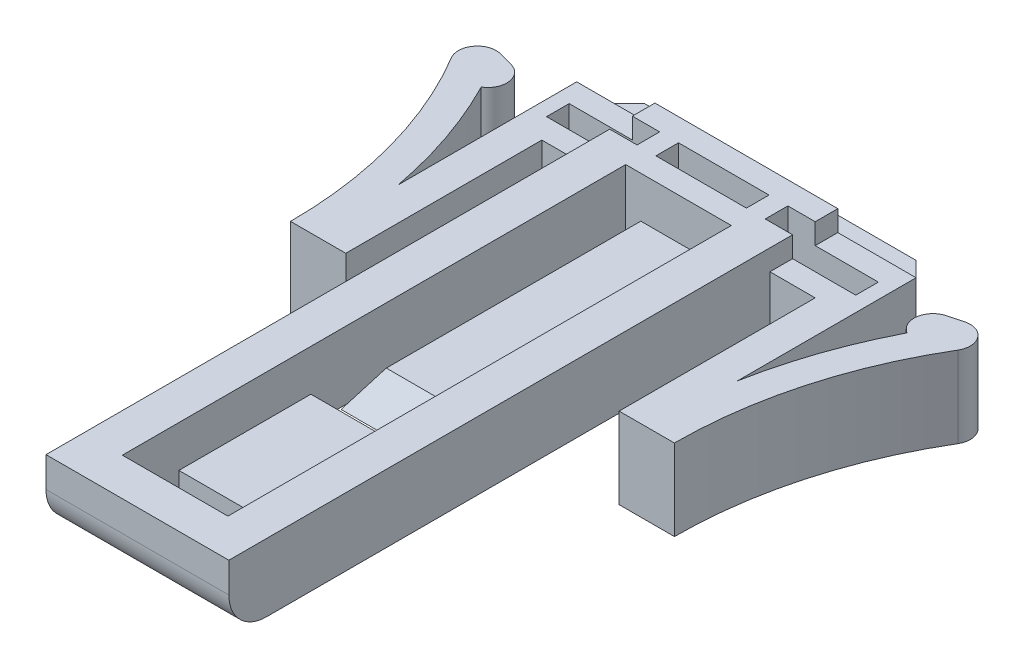
SolidWorks part; units mm, degrees
ref_plane "Спереди" through (0, 0, 0) normal (0, 0, 1) x (1, 0, 0)
ref_plane "Сверху" through (0, 0, 0) normal (0, 1, 0) x (1, 0, 0)
ref_plane "Справа" through (0, 0, 0) normal (1, 0, 0) x (0, 0, -1)
sketch "Эскиз1" plane through (0, 0, 0) normal (0, 1, 0) x (1, 0, 0)
  line L0 (0, 0) -> (0, 16.15) construction
  line L1 (4.85, 16.15) -> (-4.85, 16.15)
  line L2 (4.85, 16.15) -> (4.85, -16.15)
  line L3 (4.85, -16.15) -> (-4.85, -16.15)
  line L4 (-4.85, 16.15) -> (-4.85, -16.15)
  line L5 (4.85, 16.15) -> (-4.85, -16.15) construction
  line L6 (4.85, -16.15) -> (-4.85, 16.15) construction
  line L7 (-2.4, 14.95) -> (2.4, 14.95)
  line L8 (-2.4, 14.95) -> (-2.4, 13.75)
  line L9 (-2.4, 13.75) -> (2.4, 13.75)
  line L10 (2.4, 14.95) -> (2.4, 13.75)
  line L11 (4.85, 13.75) -> (3.4, 13.75)
  line L12 (4.85, 13.75) -> (4.85, 14.95)
  line L13 (4.85, 14.95) -> (3.4, 14.95)
  line L14 (3.4, 13.75) -> (3.4, 14.95)
  line L15 (-4.85, 13.75) -> (-3.4, 13.75)
  line L16 (-4.85, 13.75) -> (-4.85, 14.95)
  line L17 (-4.85, 14.95) -> (-3.4, 14.95)
  line L18 (-3.4, 13.75) -> (-3.4, 14.95)
  line L19 (-2, 12.55) -> (-2, -3.35)
  line L20 (-2.8, -14.15) -> (2.8, -14.15)
  line L21 (-2.8, -14.15) -> (-2.8, -11.15)
  line L22 (-2.8, -11.15) -> (2.8, -11.15)
  line L23 (2.8, -14.15) -> (2.8, -11.15)
  line L24 (2.8, -4.15) -> (-2.8, -4.15)
  line L25 (2.8, -4.15) -> (2.8, 12.55)
  line L26 (2.8, 12.55) -> (-2.8, 12.55)
  line L27 (-2.8, -4.15) -> (-2.8, 12.55)
  line L28 (-2, -3.35) -> (2, -3.35)
  line L29 (2, -3.35) -> (2, 12.55)
  point P0 (0, 0)
  dimension "D1" = 9.7
  dimension "D2" = 32.3
  dimension "D3" = 1.2
  dimension "D4" = 1.2
  dimension "D5" = 4.8
  dimension "D6" = 1
  dimension "D7" = 5.6
  dimension "D8" = 2
  dimension "D9" = 3
  dimension "D10" = 7
  dimension "D11" = 1.2
  dimension "D12" = 4
  dimension "D13" = 0.8
extrude "Бобышка-Вытянуть1" add sketch "Эскиз1" along normal blind 3.6 contours L18 L15 L4 L3 L2 L11 L14 L13 L1 L17 L23 L20 L21 L22 L7 L10 L9 L8 L24 L27 L26 L25 | L28 L29 L26 L19 region at (4.5127, 0, -15.55) region at (0, 0, -4.6)
fillet "Скругление1" radius 2 1 edges at (0, 0, 16.15)
sketch "Эскиз2" plane through (0, 0, 0) normal (0, -1, 0) x (1, 0, 0)
  line L0 (2, 3.35) -> (2, -12.55) construction
  line L1 (-2, 3.35) -> (2, 3.35)
  line L2 (-2, 3.35) -> (-2, -3.45)
  line L3 (-2, -3.45) -> (2, -3.45)
  line L4 (2, 3.35) -> (2, -3.45)
  dimension "D1" = 6.8
extrude "Бобышка-Вытянуть2" add sketch "Эскиз2" along normal blind 1.8
sketch "Эскиз3" plane through (0, 3.6, 0) normal (0, 1, 0) x (1, 0, 0)
  line L1 (2.8, -14.15) -> (-2.8, -14.15)
  line L2 (2.8, -14.15) -> (2.8, 12.55)
  line L3 (2.8, 12.55) -> (-2.8, 12.55)
  line L4 (-2.8, -14.15) -> (-2.8, 12.55)
extrude "Вырез-Вытянуть1" cut sketch "Эскиз3" against normal blind 2.2
sketch "Эскиз4" plane through (0, 0, 0) normal (1, 0, 0) x (0, 0, -1)
  line L0 (-3.35, 0.7) -> (-3.35, -1.8)
  line L1 (-3.35, 1.4) -> (-3.35, -1.8) construction
  line L2 (-3.35, -1.8) -> (0.65, -1.8)
  line L3 (-3.35, -1.8) -> (3.45, -1.8) construction
  line L4 (0.65, -1.8) -> (-3.35, 0.7)
  line L5 (-3.35, 1.4) -> (-0.95, 1.4)
  line L6 (12.55, 1.4) -> (-3.35, 1.4) construction
  line L7 (-0.95, 1.4) -> (-3.35, 0.7)
  line L8 (-3.35, 0.7) -> (-3.35, 1.4)
  line L9 (-4.15, 0.7) -> (-3.35, 0.7)
  line L10 (-4.15, 1.4) -> (-4.15, 0) construction
  line L11 (3.45, -1.8) -> (3.45, 0) construction
  point P14 (-3.35, 0.6668)
  point P18 (-3.35, 0.6714)
  dimension "D1" = 2.8
  dimension "D2" = 2.4
extrude "Вырез-Вытянуть2" cut sketch "Эскиз4" against normal mid plane 4.5 contours L2 L4 L0 | L8 L7 L5 region at (0, -0.9667, 2.0167) region at (0, 1.1667, 2.55)
ref_plane "Плоскость1" through (0, 2.5, 0) normal (0, 1, 0) x (1, 0, 0)
sketch "Эскиз5" plane through (0, 2.5, 0) normal (0, 1, 0) x (1, 0, 0)
  line L0 (-7.25, 12.55) -> (7.25, 12.55)
  line L1 (7.25, 12.55) -> (7.25, 2.15)
  line L2 (7.25, 2.15) -> (10.1812, 2.15)
  line L3 (-7.25, 12.55) -> (-7.25, 2.15)
  line L4 (-7.25, 2.15) -> (-10.1812, 2.15)
  line L5 (-9, 6.6697) -> (-9, 16.15)
  line L6 (-9, 16.15) -> (9, 16.15)
  line L7 (9, 16.15) -> (9, 6.6697)
  line L8 (0, 0) -> (0, 16.15) construction
  line L9 (4.85, 16.15) -> (-4.85, 16.15) construction
  line L10 (2.8, 12.55) -> (-2.8, 12.55) construction
  line L11 (4.85, 13.75) -> (3.4, 13.75) construction
  line L12 (-2.4, 14.95) -> (2.4, 14.95)
  line L13 (-2.4, 14.95) -> (-2.4, 13.75)
  line L14 (-2.4, 13.75) -> (2.4, 13.75)
  line L15 (2.4, 14.95) -> (2.4, 13.75)
  line L16 (3.4, 14.95) -> (8.2, 14.95)
  line L17 (3.4, 14.95) -> (3.4, 13.75)
  line L18 (3.4, 13.75) -> (8.2, 13.75)
  line L19 (8.2, 14.95) -> (8.2, 13.75)
  line L20 (-3.4, 14.95) -> (-8.2, 14.95)
  line L21 (-3.4, 14.95) -> (-3.4, 13.75)
  line L22 (-3.4, 13.75) -> (-8.2, 13.75)
  line L23 (-8.2, 14.95) -> (-8.2, 13.75)
  line L24 (-12.5727, 14.45) -> (-11.8, 14.2429) construction
  line L25 (-12.3139, 15.4159) -> (-11.5412, 15.2089)
  line L26 (-12.8316, 13.4841) -> (-12.0588, 13.277)
  line L27 (12.5727, 14.45) -> (11.8, 14.2429) construction
  line L28 (12.3139, 15.4159) -> (11.5412, 15.2089)
  line L29 (12.8316, 13.4841) -> (12.0588, 13.277)
  arc A0 (-12.3139, 15.4159) -> (-12.8316, 13.4841) centre (-12.5727, 14.45) ccw
  arc A1 (-12.0588, 13.277) -> (-11.5412, 15.2089) centre (-11.8, 14.2429) ccw
  arc A2 (-10.1812, 2.15) -> (-13.4314, 13.9375) centre (-33.1812, 2.15) ccw
  arc A3 (-9, 6.6697) -> (-11.2942, 13.3803) centre (-33.1812, 2.15) ccw
  arc A4 (12.3139, 15.4159) -> (12.8316, 13.4841) centre (12.5727, 14.45) cw
  arc A5 (12.0588, 13.277) -> (11.5412, 15.2089) centre (11.8, 14.2429) cw
  arc A6 (9, 6.6697) -> (11.2942, 13.3803) centre (33.1812, 2.15) cw
  arc A7 (10.1812, 2.15) -> (13.4314, 13.9375) centre (33.1812, 2.15) cw
  point P35 (-12.1864, 14.3465)
  point P44 (0, 0)
  point P46 (0, 0)
  point P47 (-12.7424, 12.335)
  point P48 (-9, 5.398)
  point P49 (-31.7295, 2.3883)
  point P50 (0, 0)
  point P51 (-33.8111, 2.15)
  point P52 (-33.3254, 2.15)
  point P55 (12.1864, 14.3465)
  point P64 (0, 0)
  dimension "D4" = 1
  dimension "D7" = 1.6
  dimension "D9" = 23
  dimension "D10" = 1.7
  dimension "D1" = 18
  dimension "D2" = 14.5
  dimension "D3" = 14
  dimension "D5" = 15
  dimension "D6" = 0.8
  dimension "D8" = 2.8
extrude "Бобышка-Вытянуть3" add sketch "Эскиз5" against normal blind 4.3 contours L2 A7 A4 L29 A5 A6 L7 L6 L5 A3 A1 L26 A0 A2 L4 L3 L0 L1 L16 L19 L18 L17 L12 L15 L14 L13 L23 L20 L21 L22 | A5 L29 A4 L28 | L26 A1 L25 A0 region at (-7.5529, 2.5, -7.35) region at (-12.1864, 2.5, -14.3465) region at (12.1864, 2.5, -14.3465)
sketch "Эскиз6" plane through (0, 0, 0) normal (1, 0, 0) x (0, 0, -1)
  line L0 (16.15, -1.8) -> (17.95, 1.5)
  line L1 (17.95, 1.5) -> (16.15, 1.5)
  line L2 (16.15, -1.8) -> (16.15, 2.5) construction
  line L3 (16.15, 1.5) -> (16.15, -1.8)
  dimension "D1" = 3.3
  dimension "D2" = 1.8
extrude "Бобышка-Вытянуть4" add sketch "Эскиз6" along normal mid plane 18
sketch "Эскиз7" plane through (0, 1.5, 0) normal (0, 1, 0) x (1, 0, 0)
  line L0 (9, 16.15) -> (9, 17.95)
  line L1 (9, 17.95) -> (7.2, 17.95)
  line L2 (9, 17.95) -> (-9, 17.95) construction
  line L3 (7.2, 17.95) -> (9, 16.15)
  line L4 (-9, 17.95) -> (-9, 16.15)
  line L5 (-9, 16.15) -> (-7.2, 17.95)
  line L6 (-7.2, 17.95) -> (-9, 17.95)
  dimension "D1" = 45
  dimension "D2" = 45
extrude "Вырез-Вытянуть3" cut sketch "Эскиз7" against normal through all
